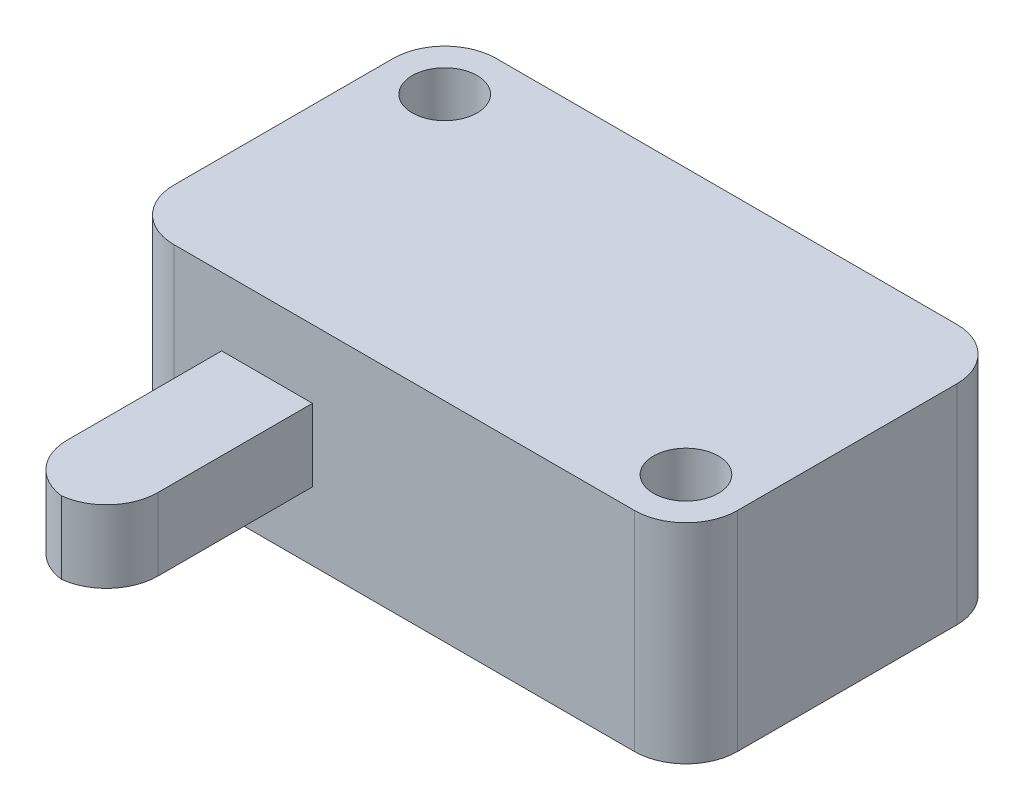
SolidWorks part; units mm, degrees
ref_plane "Front Plane" through (0, 0, 0) normal (0, 0, 1) x (1, 0, 0)
ref_plane "Top Plane" through (0, 0, 0) normal (0, 1, 0) x (1, 0, 0)
ref_plane "Right Plane" through (0, 0, 0) normal (1, 0, 0) x (0, 0, -1)
sketch "Sketch1" plane through (0, 0, 0) normal (0, 1, 0) x (1, 0, 0)
  line L1 (-13.9, -7.95) -> (13.9, -7.95)
  line L2 (-13.9, -7.95) -> (-13.9, 7.95)
  line L3 (-13.9, 7.95) -> (13.9, 7.95)
  line L4 (13.9, -7.95) -> (13.9, 7.95)
  line L5 (-13.9, -7.95) -> (13.9, 7.95) construction
  line L6 (-13.9, 7.95) -> (13.9, -7.95) construction
  point P0 (0, 0)
  dimension "D1" = 27.8
  dimension "D2" = 15.9
extrude "Boss-Extrude1" add sketch "Sketch1" along normal blind 10.3
ref_point "Point1"
ref_axis "Axis2" through (0, 10.3, 0) along (0, 1, 0)
sketch "Sketch3" plane through (0, 10.3, 0) normal (0, 1, 0) x (1, 0, 0)
  line L0 (-13.9, 7.95) -> (-13.9, 5.15) construction
  line L1 (-13.9, 7.95) -> (-13.9, -7.95) construction
  line L2 (-13.9, 5.15) -> (-11.1, 5.15) construction
  circle A0 centre (-11.1, 5.15) radius 1.6
  dimension "D2" = 3.2
  dimension "D1" = 2.8
extrude "Cut-Extrude1" cut sketch "Sketch3" against normal through all
pattern_circular "CirPattern1" count 2 over 360 about axis through (0, 10.3, 0) along (0, 1, 0) of "Cut-Extrude1"
sketch "Sketch6" plane through (0, 0, 7.95) normal (0, 0, 1) x (1, 0, 0)
  line L0 (-13.9, 5.15) -> (-9, 5.15) construction
  line L1 (-13.9, 10.3) -> (-13.9, 0) construction
  line L2 (-9, 5.15) -> (-9, 6.9356)
  line L3 (-9, 5.15) -> (-9, 3.3644)
  line L4 (-9, 6.9356) -> (-4.5238, 6.9356)
  line L5 (-4.5238, 6.9356) -> (-4.5238, 3.3644)
  line L6 (-4.5238, 3.3644) -> (-9, 3.3644)
  point P8 (-8.843, 6.9155)
  point P10 (0, 0)
  point P11 (-8.9551, 6.9079)
  point P12 (0, 0)
  point P13 (0, 0)
  point P14 (0, 0)
  point P15 (0, 0)
  point P16 (-8.9771, 6.9314)
extrude "Boss-Extrude2" add sketch "Sketch6" along normal blind 10.16
fillet "Fillet1" radius 2.54 4 edges at (-13.9, 5.15, 7.95) (-13.9, 5.15, -7.95) (13.9, 5.15, -7.95) (13.9, 5.15, 7.95)
sketch "Sketch5" plane through (0, 0, -7.95) normal (0, 0, -1) x (-1, 0, 0)
  line L0 (-13.9, 5.15) -> (-11.6198, 5.15)
  line L1 (-13.9, 10.3) -> (-13.9, 0) construction
fillet "Fillet2" radius 2.54 2 edges at (-9, 5.15, 18.11) (-4.5238, 5.15, 18.11)
